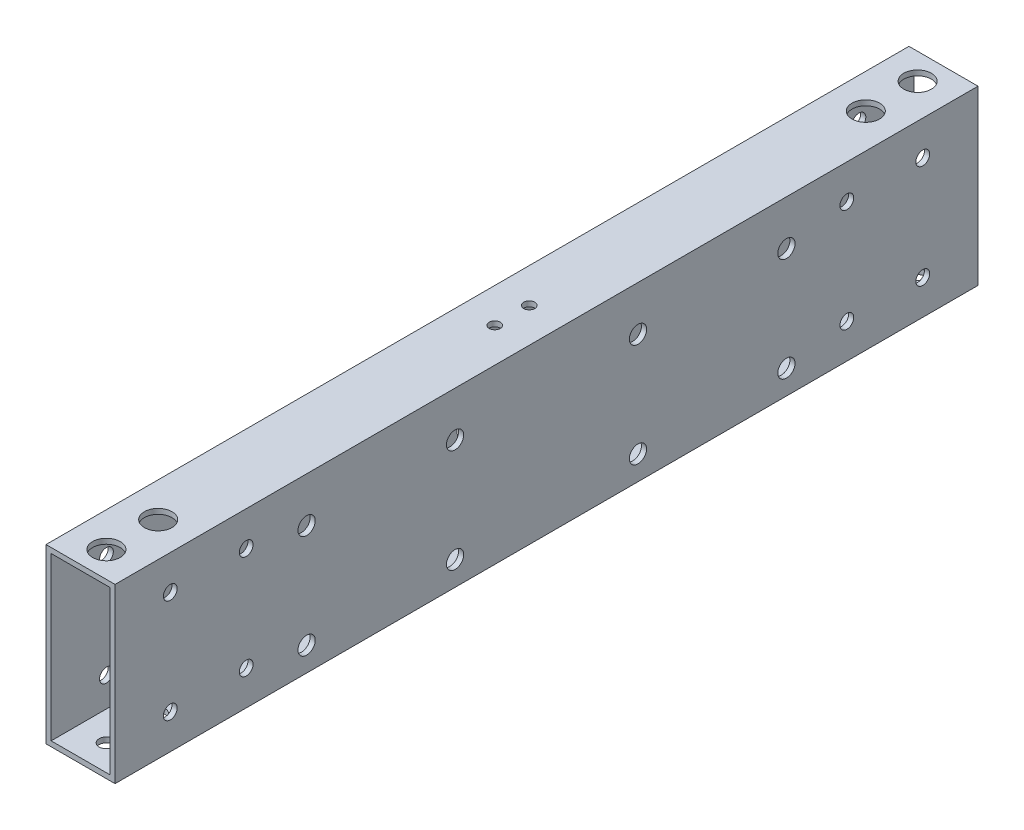
SolidWorks part; units mm, degrees
ref_plane "前视基准面" through (0, 0, 0) normal (0, 0, 1) x (1, 0, 0)
ref_plane "上视基准面" through (0, 0, 0) normal (0, 1, 0) x (1, 0, 0)
ref_plane "右视基准面" through (0, 0, 0) normal (1, 0, 0) x (0, 0, -1)
sketch "草图1" plane through (0, 0, 0) normal (0, 0, 1) x (1, 0, 0)
  line L0 (-8.5, 23.5) -> (8.5, 23.5)
  line L1 (-10, -25) -> (10, -25)
  line L2 (-10, -25) -> (-10, 25)
  line L3 (-10, 25) -> (10, 25)
  line L4 (10, -25) -> (10, 25)
  line L5 (-10, -25) -> (10, 25) construction
  line L6 (-10, 25) -> (10, -25) construction
  line L11 (8.5, -23.5) -> (8.5, 23.5)
  line L12 (-8.5, -23.5) -> (8.5, -23.5)
  line L13 (-8.5, -23.5) -> (-8.5, 23.5)
  point P9 (0, 0)
  dimension "D1" = 50
  dimension "D2" = 20
  dimension "D3" = 1.5
extrude "凸台-拉伸1" add sketch "草图1" against normal blind 250
sketch "草图2" plane through (-10, 0, 0) normal (-1, 0, 0) x (0, 0, 1)
  line L0 (-125, 20) -> (-125, -49980) construction
  line L1 (-250, 25) -> (0, 25) construction
  line L2 (-250, 25) -> (0, 25) construction
  line L11 (-55.5, -18) -> (-98.5, -18) construction
  line L13 (-55.5, -18) -> (-55.5, 12) construction
  line L14 (-55.5, 12) -> (-98.5, 12) construction
  line L15 (-98.5, -18) -> (-98.5, 12) construction
  line L16 (-55.5, -18) -> (-98.5, 12) construction
  line L17 (-55.5, 12) -> (-98.5, -18) construction
  line L18 (-71.3284, -3) -> (-50071.3284, -3) construction
  line L19 (-77, -3) -> (-77, 49997) construction
  line L20 (-194.5, 12) -> (-151.5, -18) construction
  line L21 (-194.5, -18) -> (-151.5, 12) construction
  line L22 (-151.5, -18) -> (-151.5, 12) construction
  line L23 (-194.5, 12) -> (-151.5, 12) construction
  line L24 (-194.5, -18) -> (-194.5, 12) construction
  line L25 (-194.5, -18) -> (-151.5, -18) construction
  line L26 (0, -25) -> (0, 25) construction
  circle A16 centre (-55.5, 12) radius 2.5
  circle A17 centre (-98.5, 12) radius 2.5
  circle A18 centre (-98.5, -18) radius 2.5
  circle A19 centre (-55.5, -18) radius 2.5
  circle A20 centre (-194.5, -18) radius 2.5
  circle A21 centre (-151.5, -18) radius 2.5
  circle A22 centre (-151.5, 12) radius 2.5
  circle A23 centre (-194.5, 12) radius 2.5
  point P4 (-125, 25)
  point P5 (-77, -3)
  point P28 (-173, -3)
  dimension "D4" = 5
  dimension "D5" = 77
  dimension "D2" = 43
  dimension "D1" = 30
  dimension "D3" = 28
extrude "切除-拉伸1" cut sketch "草图2" against normal through all
sketch "草图3" plane through (0, 25, 0) normal (0, 1, 0) x (1, 0, 0)
  line L0 (-10, 30) -> (49990, 30) construction
  line L2 (10, 0) -> (-10, 0) construction
  line L3 (0, 0) -> (0, 50000) construction
  line L4 (10, 125) -> (50010, 125) construction
  line L5 (10, 250) -> (10, 0) construction
  circle A0 centre (0, 22.5) radius 2.1
  circle A1 centre (0, 7.5) radius 2.1
  circle A2 centre (0, 242.5) radius 2.1
  circle A3 centre (0, 227.5) radius 2.1
  point P6 (0, 0)
  point P15 (10, 125)
  dimension "D2" = 4.2
  dimension "D3" = 4.2
  dimension "D1" = 30
  dimension "D4" = 15
  dimension "D5" = 7.5
extrude "切除-拉伸2" cut sketch "草图3" against normal through all
sketch "草图4" plane through (0, 25, 0) normal (0, 1, 0) x (1, 0, 0)
  line L0 (0, 250) -> (0, -49750) construction
  line L1 (10, 250) -> (-10, 250) construction
  line L2 (-10, 125) -> (49990, 125) construction
  line L3 (-10, 250) -> (-10, 0) construction
  circle A0 centre (0, 130) radius 1.6
  circle A1 centre (0, 120) radius 1.6
  point P4 (0, 250)
  point P9 (-10, 125)
  dimension "D1" = 3.2
  dimension "D2" = 10
extrude "切除-拉伸3" cut sketch "草图4" against normal blind 10
sketch "草图5" plane through (0, 25, 0) normal (0, 1, 0) x (1, 0, 0)
  line L0 (10, 125) -> (50010, 125) construction
  line L1 (10, 250) -> (10, 0) construction
  circle A0 centre (0, 22.5) radius 4
  circle A1 centre (0, 7.5) radius 4
  circle A2 centre (0, 242.5) radius 4
  circle A3 centre (0, 227.5) radius 4
  point P10 (10, 125)
  dimension "D1" = 8
  dimension "D2" = 8
extrude "切除-拉伸4" cut sketch "草图5" against normal blind 10
sketch "草图6" plane through (-10, 0, 0) normal (-1, 0, 0) x (0, 0, 1)
  line L0 (-125, 25) -> (-125, -75.8071) construction
  line L1 (-250, 25) -> (0, 25) construction
  circle A0 centre (-125, -4) radius 7.5
  dimension "D1" = 15
  dimension "D2" = 4
extrude "切除-拉伸5" cut sketch "草图6" against normal blind 10
sketch "草图7" plane through (-10, 0, 0) normal (-1, 0, 0) x (0, 0, 1)
  line L0 (-250, 0) -> (0, 0) construction
  line L1 (-250, 25) -> (-250, -25) construction
  line L2 (-125, 25) -> (-125, -25) construction
  line L3 (-250, 25) -> (0, 25) construction
  line L4 (-250, -25) -> (0, -25) construction
  line L5 (-250, 15) -> (0, 15) construction
  line L6 (0, 25) -> (0, -25) construction
  line L7 (-250, -15) -> (0, -15) construction
  circle A0 centre (-234, 15) radius 2
  circle A1 centre (-212, 15) radius 2
  circle A2 centre (-234, -15) radius 2
  circle A3 centre (-212, -15) radius 2
  circle A5 centre (-38, -15) radius 2
  circle A6 centre (-16, -15) radius 2
  circle A7 centre (-38, 15) radius 2
  circle A8 centre (-16, 15) radius 2
  dimension "D3" = 4
  dimension "D1" = 15
  dimension "D2" = 15
  dimension "D4" = 22
  dimension "D5" = 16
extrude "切除-拉伸6" cut sketch "草图7" against normal through all
sketch "草图8" plane through (10, 0, 0) normal (1, 0, 0) x (0, 0, -1)
  line L0 (125, 25) -> (125, -58.3352) construction
  line L1 (250, 25) -> (0, 25) construction
  line L2 (138.5, 25) -> (138.5, -3.973)
  line L3 (138.5, 25) -> (111.5, 25)
  line L4 (125, 25) -> (125, -3.973)
  line L5 (138.5, -3.973) -> (111.5, -3.973)
  line L6 (111.5, 25) -> (111.5, -3.973)
  line M24 (250, 25) -> (0, 25)
  dimension "D1" = 27
extrude "切除-拉伸7" [suppressed] cut sketch "草图8" against normal blind 37 contours L5 L2 L4 M24 | L3 L6 L5 L4
equation "\"3。2\"=3.21956"
